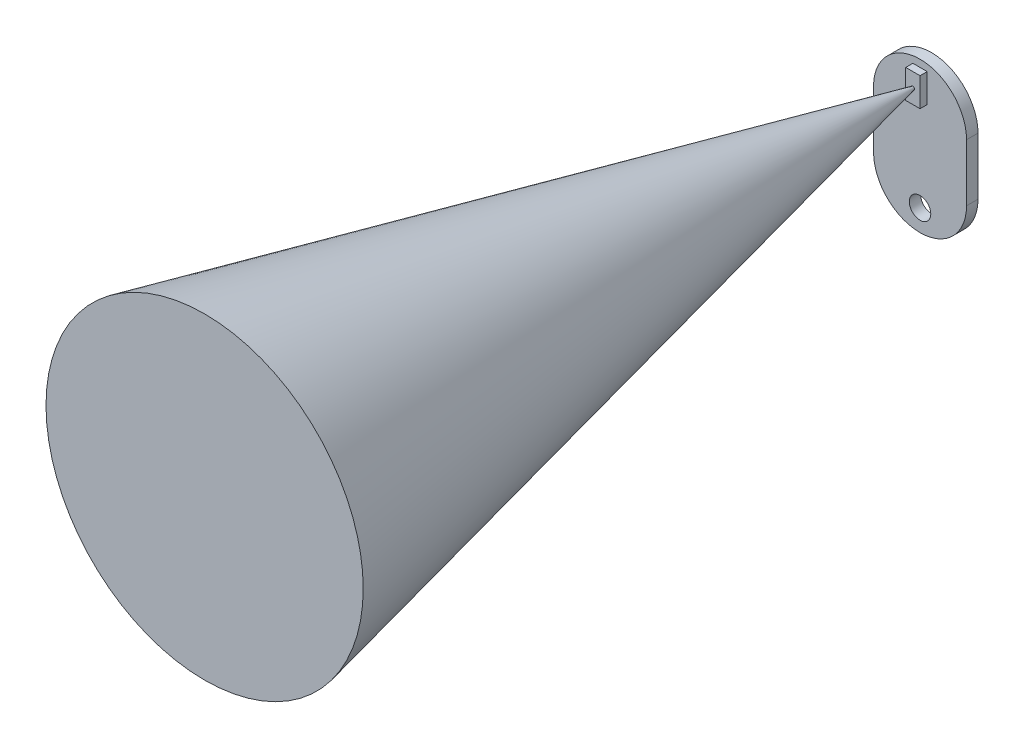
SolidWorks part; units mm, degrees
material "Fibre de verre A"
ref_plane "Plan de face" through (0, 0, 0) normal (0, 0, 1) x (1, 0, 0)
ref_plane "Plan de dessus" through (0, 0, 0) normal (0, 1, 0) x (1, 0, 0)
ref_plane "Plan de droite" through (0, 0, 0) normal (1, 0, 0) x (0, 0, -1)
sketch "Esquisse1" plane through (0, 0, 0) normal (0, 0, 1) x (1, 0, 0)
  line L0 (0, -3.5) -> (0, -11.5) construction
  line L1 (6.5, -3.5) -> (6.5, -11.5)
  line L2 (-6.5, -3.5) -> (-6.5, -11.5)
  arc A0 (6.5, -3.5) -> (-6.5, -3.5) centre (0, -3.5) ccw
  arc A1 (-6.5, -11.5) -> (6.5, -11.5) centre (0, -11.5) ccw
  circle A2 centre (0, -15) radius 1.5
  point P3 (0, -7.5)
  dimension "D2" = 21
  dimension "D4" = 3
  dimension "D1" = 13
  dimension "D3" = 3
  dimension "D5" = 3
extrude "Boss.-Extru.1" add sketch "Esquisse1" along normal blind 1.6
sketch "Esquisse2" plane through (0, 0, 1.6) normal (0, 0, 1) x (1, 0, 0)
  line L0 (-1, 2) -> (1, -2) construction
  line L1 (-1, 2) -> (1, 2)
  line L2 (-1, 2) -> (-1, -2)
  line L3 (-1, -2) -> (1, -2)
  line L4 (1, 2) -> (1, -2)
  dimension "D1" = 2
  dimension "D2" = 4
extrude "Boss.-Extru.2" add sketch "Esquisse2" along normal blind 1
sketch "Esquisse3" plane through (0, 0, 0) normal (1, 0, 0) x (0, 0, -1)
  line L0 (0, 0) -> (-21.7638, 0) construction
  line L1 (-1.6, 0) -> (-101.6, 0)
  line L2 (-101.6, 0) -> (-101.6, 22.1695)
  line L3 (-101.6, 22.1695) -> (-1.6, 0)
  line L4 (-1.6, -2) -> (-1.6, 2) construction
  dimension "D1" = 100
  dimension "D2" = 12.5
revolve "Révolution1" add sketch "Esquisse3" angle 360 about L0
